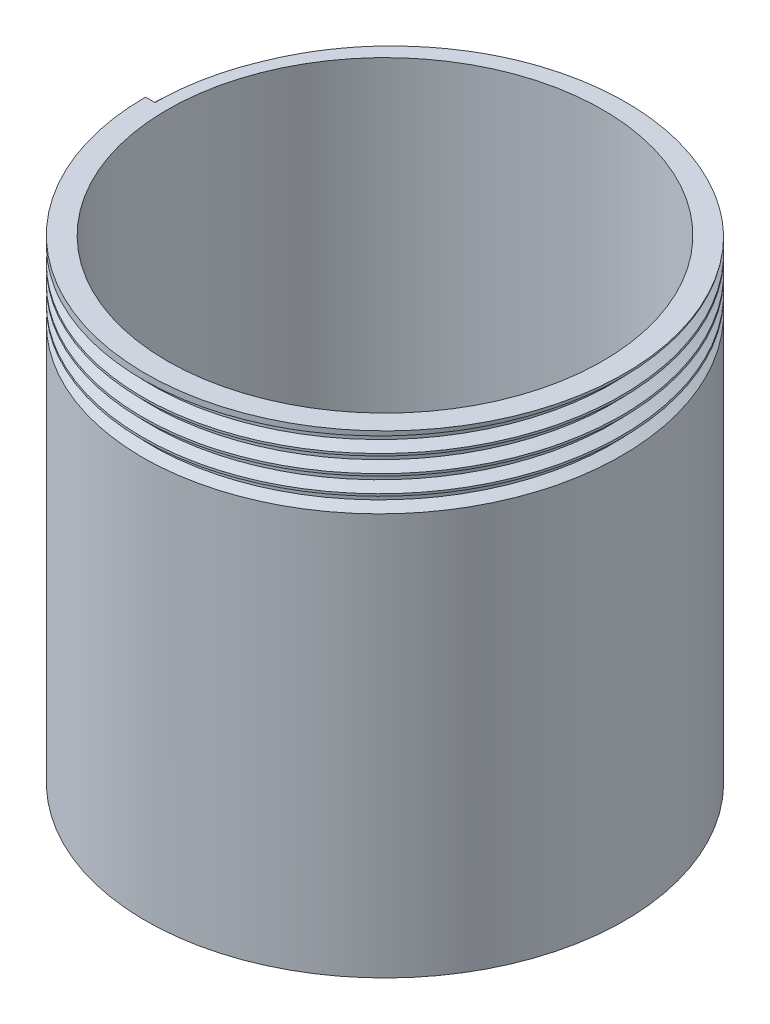
SolidWorks part; units mm, degrees
ref_plane "Front Plane" through (0, 0, 0) normal (0, 0, 1) x (1, 0, 0)
ref_plane "Top Plane" through (0, 0, 0) normal (0, 1, 0) x (1, 0, 0)
ref_plane "Right Plane" through (0, 0, 0) normal (1, 0, 0) x (0, 0, -1)
sketch "Sketch1" plane through (0, 0, 0) normal (0, 1, 0) x (1, 0, 0)
  circle A0 centre (0, 0) radius 50
  circle A1 centre (0, 0) radius 55
  dimension "D1" = 100
  dimension "D2" = 5
extrude "Boss-Extrude1" add sketch "Sketch1" along normal blind 100
sketch "Sketch2" plane through (0, 0, 0) normal (0, 1, 0) x (1, 0, 0)
  circle A0 centre (0, 0) radius 60
sketch "Sketch3" plane through (0, 0, 0) normal (0, 0, 1) x (1, 0, 0)
  line L0 (0, 0) -> (0, -8.8163) construction
  line L1 (-55, 0) -> (-5, -8.8163) construction
  line L3 (-12, -4.5358) -> (-37.7237, 0) construction
  line L4 (60, 0) -> (-60, 0) construction
  line L5 (-37.7237, 0) -> (-55, 0)
  line L6 (-12, -4.5358) -> (0, -4.5358) construction
  line L7 (0, -4.5358) -> (0, -8.8163)
  line L8 (0, -8.8163) -> (-5, -8.8163)
  line L9 (-12, -4.5358) -> (-12, -1.0358) construction
  line L10 (-12, -1.0358) -> (0, -1.0358)
  line L11 (0, -1.0358) -> (0, -4.5358)
  line L12 (-37.7237, 0) -> (-12, -1.0358)
  line L13 (-55, 0) -> (-55, -8.8163)
  line L14 (-55, -8.8163) -> (-5, -8.8163)
  line L15 (-55, 0) -> (55, 0) construction
  dimension "D1" = 3
  dimension "D2" = 10
  dimension "D3" = 12
  dimension "D4" = 5
  dimension "D5" = 3.5
revolve "Revolve1" add sketch "Sketch3" angle 360 about L0
sketch "Sketch14" plane through (0, -8.8163, 0) normal (0, -1, 0) x (1, 0, 0)
  circle A0 centre (0, 0) radius 2.5
  dimension "D1" = 5
extrude "Cut-Extrude4" cut sketch "Sketch14" against normal blind 2
sketch "Sketch15" plane through (0, 0, 0) normal (1, 0, 0) x (0, 0, -1)
  line L0 (-55, -8.8163) -> (55, -8.8163) construction
  line L4 (0, -8.8163) -> (0, -2.8163) construction
  line L16 (-2, -8.8163) -> (-2, -3.698) construction
  line L18 (-2, -8.8163) -> (-9.1017, -6.586)
  line L20 (-8.6041, -5.0842) -> (-2, -6.8163)
  line L22 (-8.1884, -2.5033) -> (-2.3711, -3.2984)
  line L23 (-2.3711, -3.2984) -> (-2.3711, 0)
  line L24 (60, 0) -> (-60, 0) construction
  line L25 (-8.3778, -4.074) -> (0, -5.6358)
  line L26 (-2, -6.8163) -> (-2, -8.8163)
  line L27 (2, -8.8163) -> (2, -3.698) construction
  line L28 (2, -6.8163) -> (2, -8.8163)
  line L29 (8.3778, -4.074) -> (0, -5.6358)
  line L30 (2.3711, -3.2984) -> (2.3711, 0)
  line L31 (8.1884, -2.5033) -> (2.3711, -3.2984)
  line L32 (8.6041, -5.0842) -> (2, -6.8163)
  line L33 (2, -8.8163) -> (9.1017, -6.586)
  line L34 (-2.3711, 0) -> (2.3711, 0)
  arc A0 (-8.6041, -5.0842) -> (-8.3778, -4.074) centre (-8.4727, -4.5832) cw
  arc A1 (-9.1017, -6.586) -> (-8.1884, -2.5033) centre (-8.4727, -4.5832) cw
  arc A2 (9.1017, -6.586) -> (8.1884, -2.5033) centre (8.4727, -4.5832) ccw
  arc A3 (8.6041, -5.0842) -> (8.3778, -4.074) centre (8.4727, -4.5832) ccw
  dimension "D1" = 6
  dimension "D2" = 2
  dimension "D3" = 2
extrude "Cut-Extrude5" cut sketch "Sketch15" against normal mid plane 3
thread "Thread1" pitch 4 start angle 0, offset 1.5, length 15, pitch 4, diameter 110
ref_plane "Plane1" through (-55, 101.5, 0) normal (0, 0, 1) x (-1, 0, 0)
sketch "Thread Profile1" plane through (-55, 101.5, 0) normal (0, 0, 1) x (-1, 0, 0)
  line L0 (0, 0) -> (0, 4) construction
  line L11 (0, 0) -> (0, 3.5)
  line L12 (0, 3.5) -> (-2.1651, 2.25)
  line L13 (-2.1651, 2.25) -> (-2.1651, 1.25)
  line L15 (-2.1651, 1.25) -> (0, 0)
  line L17 (-2.1651, 1.75) -> (0, 1.75) construction
  point P2 (0, 0)
  dimension "Pitch" = 4
  dimension "Profile_Angle" = 60
  dimension "Profile_Land" = 1
  dimension "Profile_Height" = 2.1651
sketch "Sketch21" plane through (0, -8.8163, 0) normal (0, -1, 0) x (1, 0, 0)
  line L0 (-11, 0) -> (11, 0) construction
  line L1 (0, -60.5011) -> (0, 60.5011) construction
  line L2 (-11, 2.05) -> (-8.5, 2.05)
  line L3 (-11, 2.05) -> (-11, -2.05)
  line L4 (-11, -2.05) -> (-8.5, -2.05)
  line L5 (-8.5, 2.05) -> (-8.5, -2.05)
  line L6 (8.5, 2.05) -> (8.5, -2.05)
  line L7 (11, -2.05) -> (8.5, -2.05)
  line L8 (11, 2.05) -> (11, -2.05)
  line L9 (11, 2.05) -> (8.5, 2.05)
  dimension "D1" = 4.1
  dimension "D2" = 2.5
  dimension "D3" = 22
extrude "Cut-Extrude7" cut sketch "Sketch21" against normal through all
